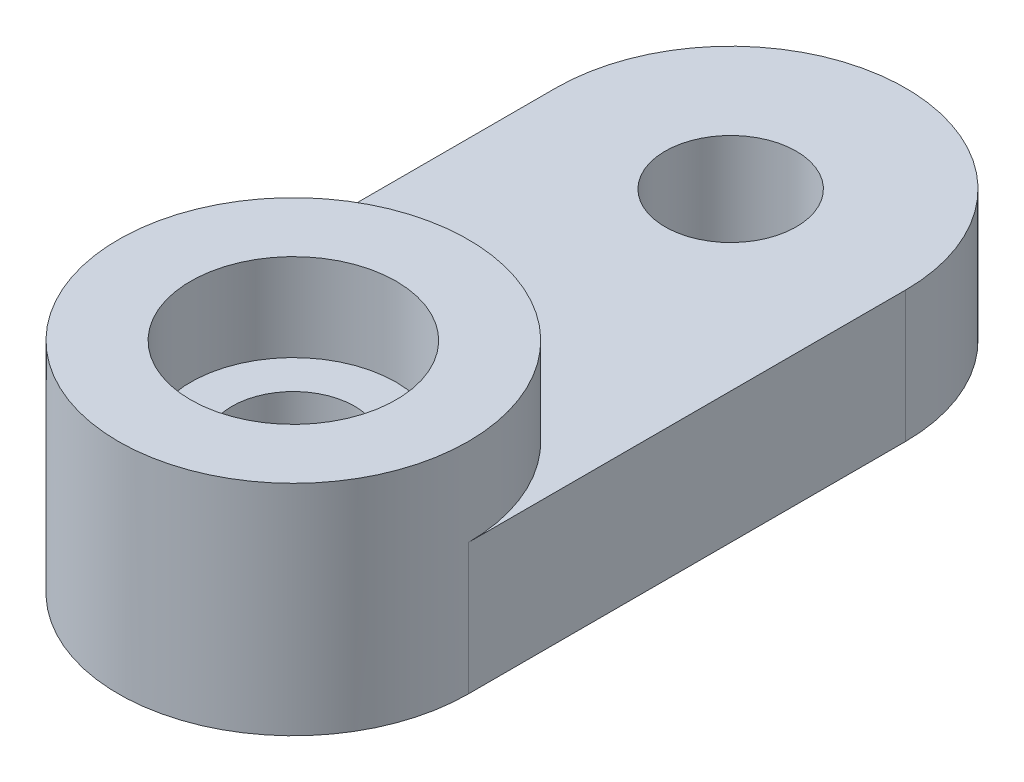
SolidWorks part; units mm, degrees
ref_plane "Front Plane" through (0, 0, 0) normal (0, 0, 1) x (1, 0, 0)
ref_plane "Top Plane" through (0, 0, 0) normal (0, 1, 0) x (1, 0, 0)
ref_plane "Right Plane" through (0, 0, 0) normal (1, 0, 0) x (0, 0, -1)
sketch "Sketch1" plane through (0, 0, 0) normal (0, 1, 0) x (1, 0, 0)
  line L0 (0, 0) -> (0, 12.7) construction
  line L1 (-5.08, 0) -> (-5.08, 12.7)
  line L2 (5.08, 0) -> (5.08, 12.7)
  circle A0 centre (0, 0) radius 1.778
  arc A1 (-5.08, 0) -> (5.08, 0) centre (0, 0) ccw
  arc A2 (5.08, 12.7) -> (-5.08, 12.7) centre (0, 12.7) ccw
  circle A3 centre (0, 12.7) radius 1.905
  point P3 (0, 6.35)
  dimension "D1" = 3.556
  dimension "D2" = 12.7
  dimension "D3" = 10.16
  dimension "D4" = 3.81
extrude "base" add sketch "Sketch1" along normal blind 3.81
sketch "Sketch2" plane through (0, 3.81, 0) normal (0, 1, 0) x (1, 0, 0)
  circle A0 centre (0, 0) radius 5.08
  arc A1 (-5.08, 0) -> (5.08, 0) centre (0, 0) ccw construction
  circle A2 centre (0, 0) radius 2.9845
  dimension "D1" = 5.969
extrude "Boss-Extrude2" add sketch "Sketch2" along normal blind 2.54
